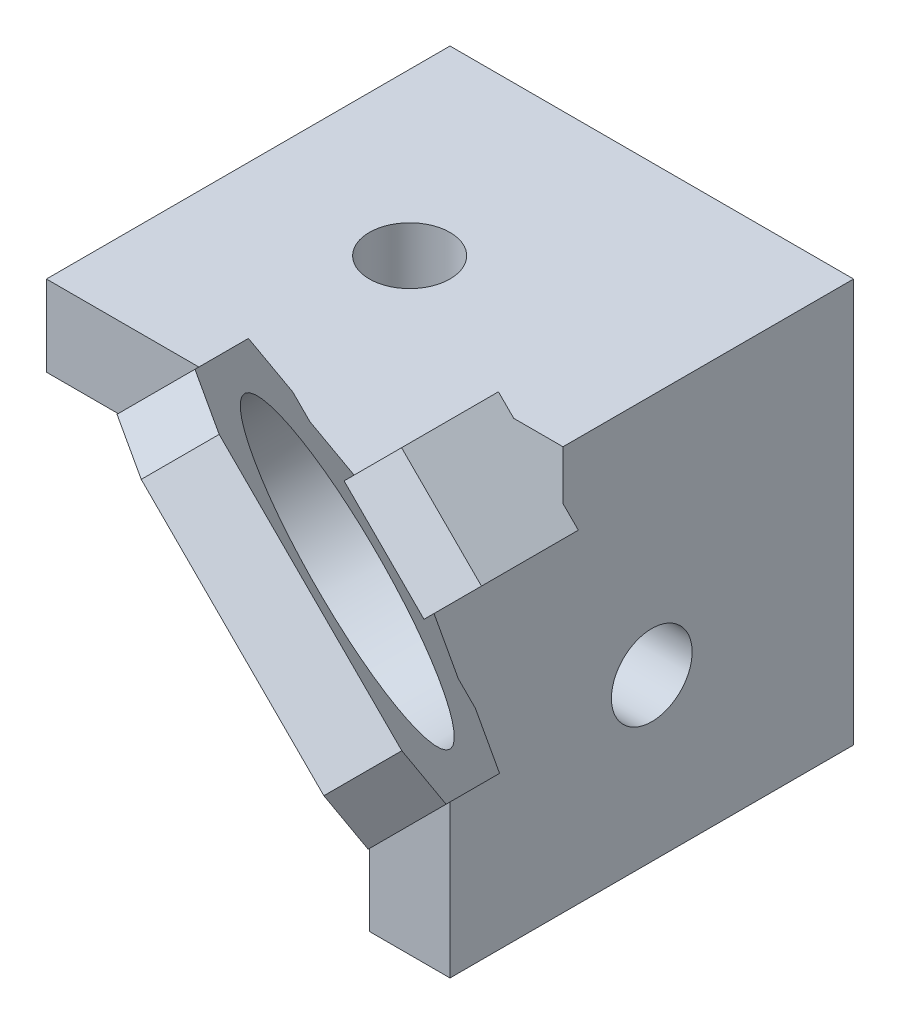
SolidWorks part; units mm, degrees
ref_plane "前视基准面" through (0, 0, 0) normal (0, 0, 1) x (1, 0, 0)
ref_plane "上视基准面" through (0, 0, 0) normal (0, 1, 0) x (1, 0, 0)
ref_plane "右视基准面" through (0, 0, 0) normal (1, 0, 0) x (0, 0, -1)
sketch "草图7" plane through (0, 0, 0) normal (0, 0, 1) x (1, 0, 0)
  line L1 (12.5, -12.5) -> (-12.5, -12.5)
  line L2 (12.5, -12.5) -> (12.5, 12.5)
  line L3 (12.5, 12.5) -> (-12.5, 12.5)
  line L4 (-12.5, -12.5) -> (-12.5, 12.5)
  line L5 (12.5, -12.5) -> (-12.5, 12.5) construction
  line L6 (12.5, 12.5) -> (-12.5, -12.5) construction
  point P0 (0, 0)
  dimension "D1" = 25
  dimension "D2" = 25
extrude "凸台-拉伸4" add sketch "草图7" along normal blind 25
sketch "草图8" plane through (0, 0, 25) normal (0, 0, 1) x (1, 0, 0)
  line L1 (-12.5, -12.5) -> (7.5, -12.5)
  line L2 (-12.5, -12.5) -> (-12.5, 7.5)
  line L3 (-12.5, 7.5) -> (7.5, 7.5)
  line L4 (7.5, -12.5) -> (7.5, 7.5)
  dimension "D1" = 20
  dimension "D2" = 20
extrude "切除-拉伸1" cut sketch "草图8" against normal blind 25
sketch "草图10" plane through (0, 0, 25) normal (0, 0, 1) x (1, 0, 0)
  line L0 (7.5, 7.5) -> (12.5, 12.5) construction
  line L1 (7.5503, 12.5) -> (12.5, 7.5503)
  line L2 (12.5, 12.5) -> (-12.5, 12.5) construction
  line L3 (12.5, -12.5) -> (12.5, 12.5) construction
  line L4 (12.5, 7.5503) -> (17.4497, 12.5)
  line L5 (17.4497, 12.5) -> (12.5, 17.4497)
  line L6 (12.5, 17.4497) -> (7.5503, 12.5)
extrude "凸台-拉伸5" add sketch "草图10" along normal blind 10 and the other way blind 3
sketch "草图12" plane through (2.4749, -2.4749, 0) normal (0.7071, -0.7071, 0) x (0, 0, -1)
  line L0 (-35, 14.1777) -> (-28, 21.1777)
  line L1 (-22, 21.1777) -> (-35, 21.1777) construction
  line L2 (-25, 14.1777) -> (-35, 14.1777) construction
  line L8 (-22, 21.1777) -> (-35, 21.1777)
  line L9 (-35, 21.1777) -> (-35, 14.1777)
  line L10 (-35, 14.1777) -> (-25, 14.1777)
  line L11 (-25, 14.1777) -> (-22, 14.1777)
  line L12 (-22, 14.1777) -> (-22, 21.1777)
  line L13 (-22, 21.1777) -> (-35, 21.1777)
  line L14 (-35, 21.1777) -> (-35, 14.1777)
  line L15 (-35, 14.1777) -> (-25, 14.1777)
  line L16 (-25, 14.1777) -> (-22, 14.1777)
  line L17 (-22, 14.1777) -> (-22, 21.1777)
  line M7 (-22, 21.1777) -> (-35, 21.1777)
  line M8 (-35, 21.1777) -> (-35, 14.1777)
  dimension "D1" = 45
  dimension "D2" = 0
extrude "切除-拉伸2" cut sketch "草图12" against normal blind 10 contours L0 M8 M7 region at (15.7998, 10.8501, 32.6667)
sketch "草图14" plane through (17.3869, 17.3869, 24.5888) normal (0.5, 0.5, 0.7071) x (0.866, -0.2887, -0.4082)
  line L0 (-2.7852, -3.9389) -> (-8.5007, -12.0218) construction
  line L1 (-5.6429, -14.0425) -> (-3.7457, -11.3594)
  line L3 (-14.6244, -1.6295) -> (-13.4697, 0.0035)
  line L6 (-1.7486, -8.5351) -> (-3.7457, -11.3594)
  line L7 (-14.6244, -1.6295) -> (-15.7791, -3.2625)
  line L8 (-15.7791, -3.2625) -> (-9.6554, -7.5926)
  line L9 (-13.4697, 0.0035) -> (-7.346, -4.3266)
  line L10 (-5.6429, -1.9181) -> (-11.3584, -10.0011)
  line L11 (-11.3584, -10.0011) -> (-5.6429, -14.0425)
  line L12 (-5.6429, -14.0425) -> (0.0725, -5.9596)
  line L13 (0.0725, -5.9596) -> (-5.6429, -1.9181)
  line L14 (-7.346, -4.3266) -> (-9.6554, -7.5926)
  line L15 (-11.3584, -10.0011) -> (-5.6429, -14.0425)
  line L16 (-5.6429, -14.0425) -> (0.0725, -5.9596)
  line L17 (0.0725, -5.9596) -> (-5.6429, -1.9181)
  line L18 (4.4932, -12.6982) -> (-1.6305, -8.3681)
  line L19 (3.3385, -14.3312) -> (4.4932, -12.6982)
  line L20 (3.3385, -14.3312) -> (2.1838, -15.9642)
  line L21 (2.1838, -15.9642) -> (-3.9399, -11.634)
  line L22 (-1.6305, -8.3681) -> (-3.9399, -11.634)
  line L23 (-9.6554, -7.5926) -> (-3.9399, -11.634)
  line L24 (-1.6305, -8.3681) -> (-7.346, -4.3266)
  line M5 (-5.6429, -1.9181) -> (-11.3584, -10.0011)
  line M7 (-5.6429, -14.0425) -> (0.0725, -5.9596)
  dimension "D1" = 0
extrude "凸台-拉伸6" add sketch "草图14" along normal blind 22 contours L9 L3 L7 L8 M5 | L0 L24 L23 M5 | L24 L0 L23 L16 M7 | L21 L20 L19 L18 L16 M7 region at (13.7374, 11.2626, 31.5) region at (11.2626, 13.7374, 31.5) region at (17.6265, 7.3735, 31.5) region at (7.3735, 17.6265, 31.5)
sketch "草图15" plane through (-5.8869, -5.8869, 8.3254) normal (-0.5, -0.5, 0.7071) x (0.866, -0.2887, 0.4082)
  line L0 (23.7969, 52.7065) -> (29.0582, 22.0419)
  circle A0 centre (26.4276, 37.3742) radius 9
extrude "切除-拉伸3" cut sketch "草图15" against normal through all contours L0 A0 | L0 A0 region at (20.2603, 16.4406, 42.6022) region at (13.7397, 17.5594, 38.7825)
sketch "草图17" plane through (2.4749, -2.4749, 0) normal (0.7071, -0.7071, 0) x (0, 0, -1)
  line L0 (-32.9142, 16.2635) -> (-25, 14.1777)
  line L8 (-32.9142, 16.2635) -> (-35, 14.1777)
  line L9 (-35, 14.1777) -> (-25, 14.1777)
  line L10 (-25, 14.1777) -> (-22, 14.1777)
  line L11 (-22, 14.1777) -> (-22, 21.1777)
  line L12 (-22, 21.1777) -> (-28, 21.1777)
  line L13 (-28, 21.1777) -> (-30.0858, 19.0919)
  line L14 (-30.0858, 19.0919) -> (-32.9142, 16.2635)
  line L15 (-32.9142, 16.2635) -> (-35, 14.1777)
  line L16 (-35, 14.1777) -> (-25, 14.1777)
  line L17 (-25, 14.1777) -> (-22, 14.1777)
  line L18 (-22, 14.1777) -> (-22, 21.1777)
  line L19 (-22, 21.1777) -> (-28, 21.1777)
  line L20 (-28, 21.1777) -> (-30.0858, 19.0919)
  line L21 (-30.0858, 19.0919) -> (-32.9142, 16.2635)
  line M9 (-32.9142, 16.2635) -> (-35, 14.1777)
  line M10 (-35, 14.1777) -> (-25, 14.1777)
  dimension "D1" = 0
extrude "切除-拉伸4" cut sketch "草图17" against normal through all contours L0 M9 M10 region at (12.9916, 8.0419, 30.9714)
chamfer "倒角1" distance 4 angle 45 3 edges at (10.0251, 12.5, 22) (12.5, 10.0251, 22) (10.0251, 10.0251, 25) first distance on face at (2.5168, 12.5, 15.6667) first distance on face at (12.5, 2.5168, 15.6667) first distance on face at (3.2215, 3.2215, 25)
chamfer "倒角2" distance 3 angle 45 6 edges at (15.7218, 31.2782, 47.0563) (31.2782, 15.7218, 47.0563) (4.7218, 20.2782, 31.5) (20.2782, 4.7218, 31.5) (14.9749, 10.0251, 31.5) (10.0251, 14.9749, 31.5)
sketch "草图19" plane through (0, 7.5, 0) normal (0, -1, 0) x (1, 0, 0)
  line L0 (7.5, 0) -> (-12.5, 0) construction
  line L1 (-12.5, 25) -> (7.5, 0) construction
  circle A0 centre (-2.5, 12.5) radius 2.5
  dimension "D1" = 5
extrude "切除-拉伸5" cut sketch "草图19" against normal through all
sketch "草图20" plane through (7.5, 0, 0) normal (-1, 0, 0) x (0, 0, 1)
  line L0 (0, 7.5) -> (25, -12.5) construction
  circle A0 centre (12.5, -2.5) radius 2.5
  dimension "D1" = 5
extrude "切除-拉伸6" cut sketch "草图20" against normal through all contours A0
